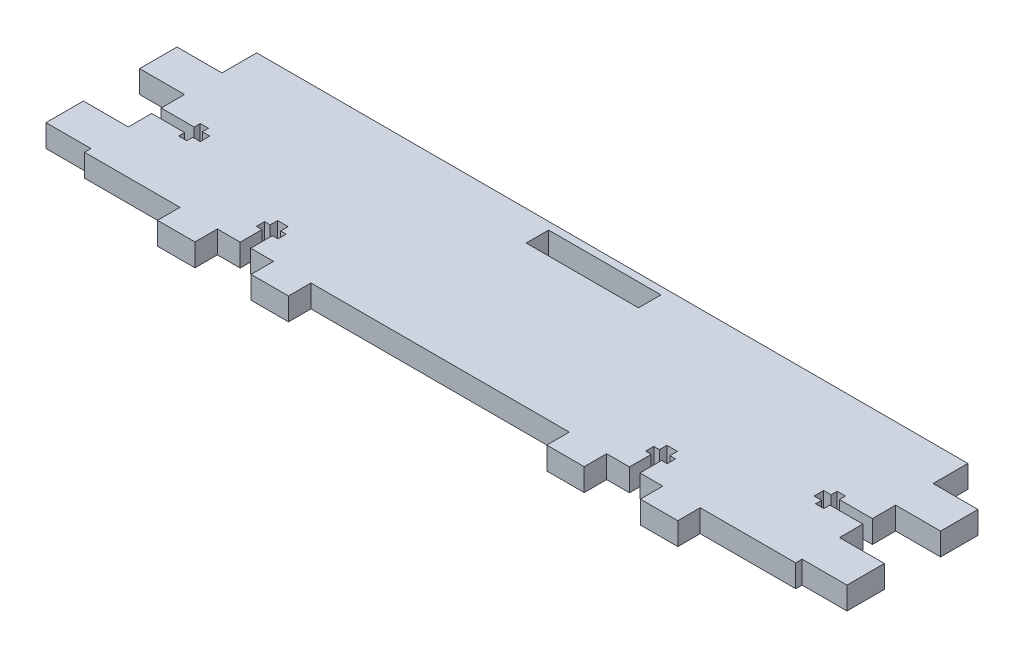
SolidWorks part; units mm, degrees
ref_plane "Front" through (0, 0, 0) normal (0, 0, 1) x (1, 0, 0)
ref_plane "Top" through (0, 0, 0) normal (0, 1, 0) x (1, 0, 0)
ref_plane "Right" through (0, 0, 0) normal (1, 0, 0) x (0, 0, -1)
sketch "Эскиз1" plane through (0, 0, 0) normal (0, 1, 0) x (1, 0, 0)
  line L0 (-131.8881, 0) -> (137.6783, 0) construction
  line L1 (-95, 23) -> (95, 23)
  line L2 (-95, 23) -> (-95, 13.7093)
  line L3 (-95, -23) -> (-69.5, -23)
  line L4 (95, 23) -> (95, 13.7093)
  line L5 (-95, 23) -> (95, -23) construction
  line L6 (-95, -23) -> (95, 23) construction
  line L7 (0, 62.5664) -> (0, -52.5944) construction
  line L8 (69.5, 51.8234) -> (69.5, -44.3584) construction
  line L9 (59.5, 51.8234) -> (59.5, -44.3584) construction
  line L10 (34.5, 51.8234) -> (34.5, -44.3584) construction
  line L11 (44.5, 51.8234) -> (44.5, -44.3584) construction
  line L12 (106.5886, -29) -> (-1.3442, -29) construction
  line L13 (59.5, -23) -> (59.5, -29)
  line L14 (59.5, -29) -> (69.5, -29)
  line L15 (69.5, -29) -> (69.5, -23)
  line L16 (34.5, -23) -> (34.5, -29)
  line L17 (34.5, -29) -> (44.5, -29)
  line L18 (44.5, -29) -> (44.5, -23)
  line L19 (52, -9.9523) -> (52, -35.233) construction
  line L20 (44.5, -23) -> (50.6, -23)
  line L21 (69.5, -23) -> (95, -23)
  line L22 (102.7865, -17.2) -> (39.4134, -17.2) construction
  line L23 (103.2055, -15) -> (39.8324, -15) construction
  line L24 (103.3102, -13) -> (39.9371, -13) construction
  line L25 (50.6, -27.2711) -> (50.6, -9.9523) construction
  line L26 (49.1, -27.2711) -> (49.1, -9.9523) construction
  line L27 (50.6, -23) -> (50.6, -17.2)
  line L28 (50.6, -17.2) -> (49.1, -17.2)
  line L29 (49.1, -17.2) -> (49.1, -15)
  line L30 (49.1, -15) -> (50.6, -15)
  line L31 (50.6, -15) -> (50.6, -13)
  line L32 (50.6, -13) -> (53.4, -13)
  line L33 (53.4, -23) -> (53.4, -17.2)
  line L34 (53.4, -17.2) -> (54.9, -17.2)
  line L35 (54.9, -17.2) -> (54.9, -15)
  line L36 (54.9, -15) -> (53.4, -15)
  line L37 (53.4, -15) -> (53.4, -13)
  line L38 (53.4, -23) -> (59.5, -23)
  line L39 (-50.6, -17.2) -> (-49.1, -17.2)
  line L40 (-49.1, -17.2) -> (-49.1, -15)
  line L41 (-49.1, -15) -> (-50.6, -15)
  line L42 (-50.6, -15) -> (-50.6, -13)
  line L43 (-50.6, -13) -> (-53.4, -13)
  line L44 (-53.4, -15) -> (-53.4, -13)
  line L45 (-54.9, -15) -> (-53.4, -15)
  line L46 (-54.9, -17.2) -> (-54.9, -15)
  line L47 (-53.4, -17.2) -> (-54.9, -17.2)
  line L48 (-53.4, -23) -> (-53.4, -17.2)
  line L49 (-50.6, -23) -> (-50.6, -17.2)
  line L50 (-34.5, -23) -> (-34.5, -29)
  line L51 (-34.5, -29) -> (-44.5, -29)
  line L52 (-44.5, -29) -> (-44.5, -23)
  line L53 (-59.5, -23) -> (-59.5, -29)
  line L54 (-59.5, -29) -> (-69.5, -29)
  line L55 (-69.5, -29) -> (-69.5, -23)
  line L56 (-59.5, -23) -> (-53.4, -23)
  line L57 (-50.6, -23) -> (-44.5, -23)
  line L58 (-34.5, -23) -> (34.5, -23)
  line L59 (107, 23) -> (107, -23) construction
  line L60 (-15, 21) -> (15, 21)
  line L61 (-15, 21) -> (-15, 15)
  line L62 (-15, 15) -> (15, 15)
  line L63 (15, 21) -> (15, 15)
  line L64 (-15, 21) -> (15, 15) construction
  line L65 (-15, 15) -> (15, 21) construction
  line L66 (119.5315, -21.2907) -> (95, -21.2907) construction
  line L67 (95, -21.2907) -> (107, -21.2907)
  line L68 (107, -21.2907) -> (107, -11.2907)
  line L69 (107, -11.2907) -> (95, -11.2907)
  line L70 (119.5315, 3.7093) -> (89.9629, 3.7093) construction
  line L71 (95, 3.7093) -> (107, 3.7093)
  line L72 (107, 3.7093) -> (107, 13.7093)
  line L73 (107, 13.7093) -> (95, 13.7093)
  line L74 (95, 3.7093) -> (95, -2.519)
  line L75 (95, -21.2907) -> (95, -23)
  line L76 (119.5315, -3.7907) -> (75.4928, -3.7907) construction
  line L77 (111.868, -2.519) -> (75.4928, -2.519) construction
  line L78 (111.868, -0.9012) -> (75.4928, -0.9012) construction
  line L79 (82, 3.0697) -> (82, -8.7695) construction
  line L80 (84, 3.0697) -> (84, -8.7695) construction
  line L81 (86.2, 3.0697) -> (86.2, -8.7695) construction
  line L82 (82, -5.0625) -> (82, -2.519)
  line L83 (82, -2.519) -> (84, -2.519)
  line L84 (84, -2.519) -> (84, -0.9012)
  line L85 (84, -0.9012) -> (86.2, -0.9012)
  line L86 (86.2, -0.9012) -> (86.2, -2.519)
  line L87 (86.2, -2.519) -> (95, -2.519)
  line L88 (82, -5.0625) -> (84, -5.0625)
  line L89 (84, -5.0625) -> (84, -6.6803)
  line L90 (84, -6.6803) -> (86.2, -6.6803)
  line L91 (86.2, -6.6803) -> (86.2, -5.0625)
  line L92 (86.2, -5.0625) -> (95, -5.0625)
  line L93 (95, -5.0625) -> (95, -11.2907)
  line L94 (-84, -6.6803) -> (-86.2, -6.6803)
  line L95 (-84, -5.0625) -> (-84, -6.6803)
  line L96 (-82, -5.0625) -> (-84, -5.0625)
  line L97 (-82, -5.0625) -> (-82, -2.519)
  line L98 (-82, -2.519) -> (-84, -2.519)
  line L99 (-84, -2.519) -> (-84, -0.9012)
  line L100 (-84, -0.9012) -> (-86.2, -0.9012)
  line L101 (-86.2, -0.9012) -> (-86.2, -2.519)
  line L102 (-86.2, -6.6803) -> (-86.2, -5.0625)
  line L103 (-86.2, -5.0625) -> (-95, -5.0625)
  line L104 (-86.2, -2.519) -> (-95, -2.519)
  line L105 (-95, -21.2907) -> (-107, -21.2907)
  line L106 (-107, -21.2907) -> (-107, -11.2907)
  line L107 (-107, -11.2907) -> (-95, -11.2907)
  line L108 (-95, 3.7093) -> (-107, 3.7093)
  line L109 (-107, 3.7093) -> (-107, 13.7093)
  line L110 (-107, 13.7093) -> (-95, 13.7093)
  line L111 (-95, 3.7093) -> (-95, -2.519)
  line L112 (-95, -5.0625) -> (-95, -11.2907)
  line L113 (-95, -21.2907) -> (-95, -23)
  point P0 (0, 0)
  point P47 (49.85, -15)
  point P53 (52, -13)
  point P57 (-49.85, -15)
  point P75 (0, 18)
  point P113 (82, -3.7907)
  dimension "D2" = 190
  dimension "D3" = 25.5
  dimension "D4" = 10
  dimension "D5" = 15
  dimension "D6" = 10
  dimension "D7" = 6
  dimension "D8" = 7.5
  dimension "D9" = 10
  dimension "D10" = 2
  dimension "D11" = 2.2
  dimension "D12" = 1.4
  dimension "D13" = 1.5
  dimension "D14" = 6
  dimension "D15" = 30
  dimension "D16" = 2
  dimension "D17" = 12
  dimension "D18" = 10
  dimension "D19" = 15
  dimension "D20" = 10
  dimension "D21" = 7.5
  dimension "D22" = 13
  dimension "D23" = 2
  dimension "D24" = 2.2
extrude "Бобышка-Вытянуть1" add sketch "Эскиз1" along normal blind 6
